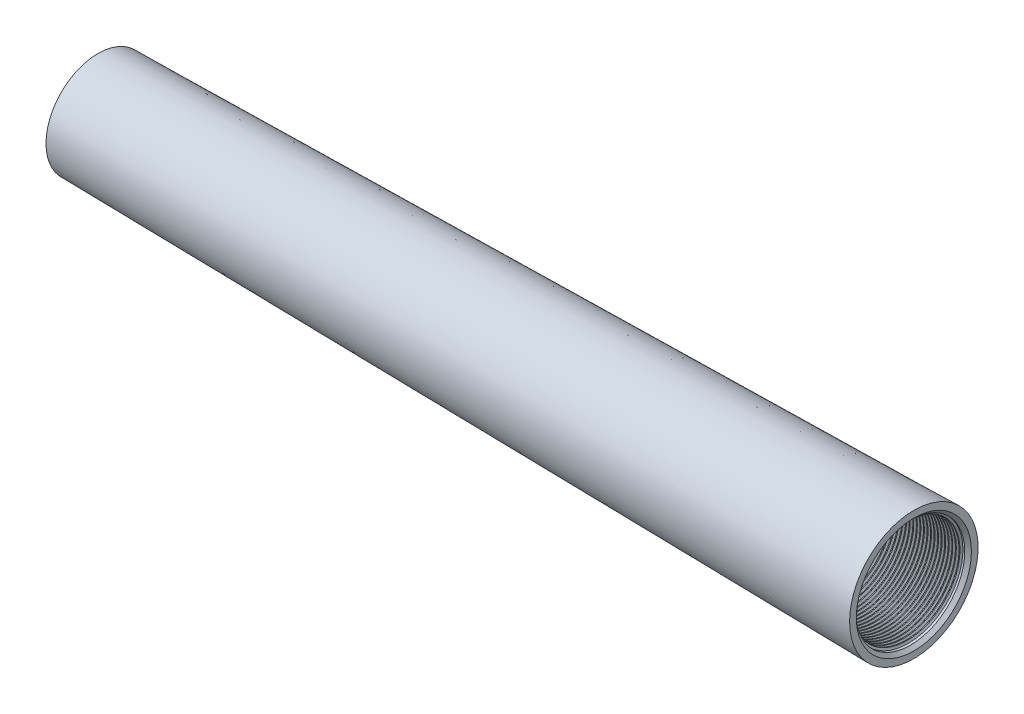
SolidWorks part; units mm, degrees
ref_plane "Front Plane" through (0, 0, 0) normal (0, 0, 1) x (1, 0, 0)
ref_plane "Top Plane" through (0, 0, 0) normal (0, 1, 0) x (1, 0, 0)
ref_plane "Right Plane" through (0, 0, 0) normal (1, 0, 0) x (0, 0, -1)
sketch "Sketch1" plane through (0, 0, 0) normal (0, 0, 1) x (1, 0, 0)
  line L0 (0, 4.65) -> (73, 5.75)
  line L1 (73, 5.75) -> (73, 3.17)
  line L2 (73, 3.17) -> (0, 3.17)
  line L3 (0, 3.17) -> (0, 4.65)
  line L4 (0, 0) -> (197.8963, 0) construction
  line L5 (73, 4.85) -> (61.5, 4.85)
  line L6 (61.5, 4.85) -> (61.5, 3.17)
  line L7 (0, 3.17) -> (0, 0) construction
  dimension "D1" = 4.65
  dimension "D2" = 11.5
  dimension "D3" = 73
  dimension "D4" = 3.17
  dimension "D5" = 4.85
  dimension "D6" = 5.75
revolve "Revolve1" add sketch "Sketch1" angle 360 about L4 region at (35.6806, 4.2398, 0)
chamfer "Chamfer1" distance 0.3 angle 45 1 edges at (73, 0, 4.85)
thread "Thread1" pitch 0.3175 method extrude profile "Thread Profile1" start angle 0, offset 0, length 10, pitch 0.3175, diameter 9.7
ref_plane "Plane1" through (72.7, 0, 4.85) normal (0, -1, 0) x (0, 0, 1)
sketch "Thread Profile1" plane through (72.7, 0, 4.85) normal (0, -1, 0) x (0, 0, 1)
  line L0 (0, 0) -> (0, 0.3175) construction
  line L11 (0, 0) -> (0, 0.2778)
  line L12 (0, 0.2778) -> (-0.1719, 0.1786)
  line L13 (-0.1719, 0.1786) -> (-0.1719, 0.0992)
  line L15 (-0.1719, 0.0992) -> (0, 0)
  line L17 (-0.1719, 0.1389) -> (0, 0.1389) construction
  point P2 (0, 0)
  dimension "Pitch" = 0.3175
  dimension "Profile_Angle" = 60
  dimension "Profile_Land" = 0.0794
  dimension "Profile_Height" = 0.1719
